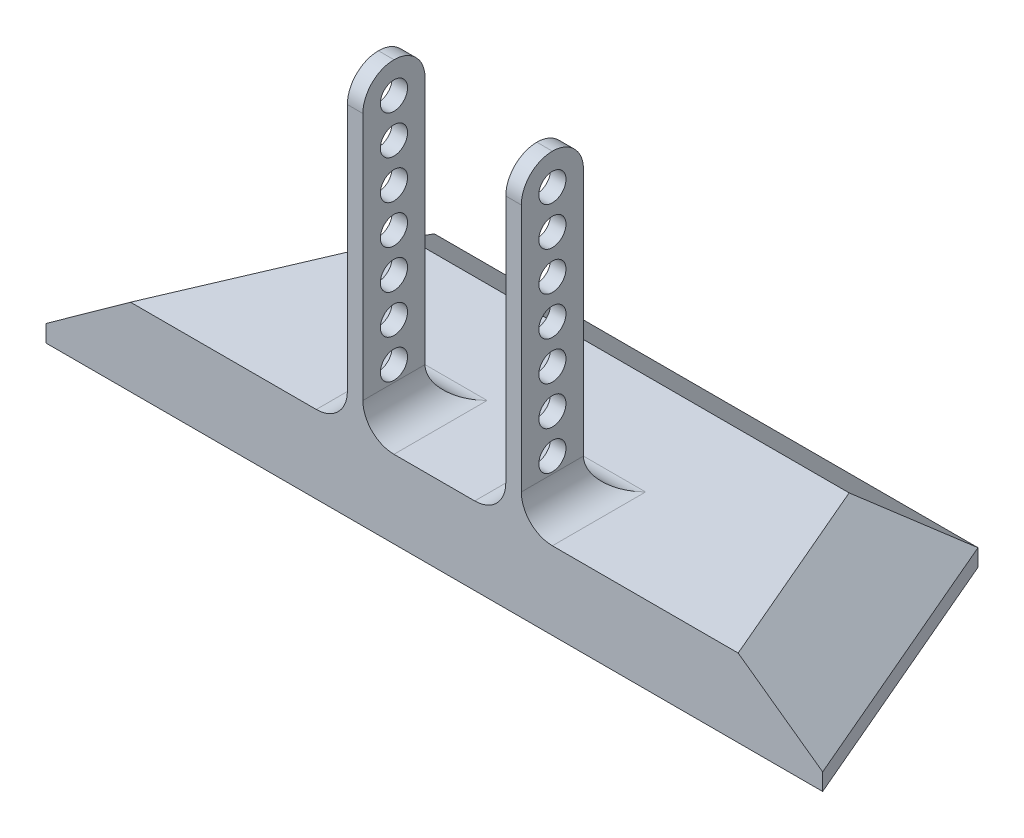
SolidWorks part; units mm, degrees
ref_plane "Front Plane" through (0, 0, 0) normal (0, 0, 1) x (1, 0, 0)
ref_plane "Top Plane" through (0, 0, 0) normal (0, 1, 0) x (1, 0, 0)
ref_plane "Right Plane" through (0, 0, 0) normal (1, 0, 0) x (0, 0, -1)
sketch "Sketch1" plane through (0, 0, 0) normal (0, 1, 0) x (1, 0, 0)
  line L1 (-50, 17.5) -> (50, 17.5)
  line L2 (-50, 17.5) -> (-50, -17.5)
  line L3 (-50, -17.5) -> (50, -17.5)
  line L4 (50, 17.5) -> (50, -17.5)
  line L5 (-50, 17.5) -> (50, -17.5) construction
  line L6 (-50, -17.5) -> (50, 17.5) construction
  point P0 (0, 0)
  dimension "D1" = 35
  dimension "D2" = 100
extrude "Boss-Extrude1" add sketch "Sketch1" along normal blind 10
sketch "Sketch2" plane through (0, 10, 0) normal (0, 1, 0) x (1, 0, 0)
  line L0 (-50, 17.5) -> (-35, 17.5)
  line L1 (50, 17.5) -> (-50, 17.5) construction
  line L2 (-35, 17.5) -> (-50, -17.5)
  line L3 (-50, -17.5) -> (-50, 17.5)
  line L4 (50, 17.5) -> (35, 17.5)
  line L5 (35, 17.5) -> (50, -17.5)
  line L6 (50, -17.5) -> (50, 17.5)
  dimension "D1" = 15
  dimension "D2" = 15
extrude "Cut-Extrude1" cut sketch "Sketch2" against normal through all
chamfer "Chamfer1" distance 10 angle 38 3 edges at (42.5, 10, 0) (-42.5, 10, 0) (0, 10, -17.5) first distance on face at (0, 10, 0)
sketch "Sketch3" plane through (0, 10, 0) normal (0, 1, 0) x (1, 0, 0)
  line L0 (-39.1203, -17.5) -> (39.1203, -17.5) construction
  line L1 (-9.2, -17.5) -> (-11.2, -17.5)
  line L2 (-9.2, -17.5) -> (-9.2, -9.5)
  line L3 (-9.2, -9.5) -> (-11.2, -9.5)
  line L4 (-11.2, -17.5) -> (-11.2, -9.5)
  dimension "D1" = 9.2
  dimension "D2" = 2
  dimension "D3" = 8
extrude "Boss-Extrude2" add sketch "Sketch3" along normal blind 40
fillet "Fillet1" radius 4 2 edges at (-10.2, 50, 9.5) (-10.2, 50, 17.5)
sketch "Sketch4" plane through (-11.2, 0, 0) normal (-1, 0, 0) x (0, 0, 1)
  line L0 (9.5, 46) -> (9.5, 10) construction
  circle A0 centre (13.5, 46) radius 1.75
  dimension "D2" = 3.5
  dimension "D1" = 4
  dimension "D3" = 4
extrude "Cut-Extrude2" cut sketch "Sketch4" against normal through all
pattern_linear "LPattern1" count 7 spacing 5 along (0, -1, 0) of "Cut-Extrude2"
mirror "Mirror1" about plane through (0, 0, 0) normal (1, 0, 0) of "LPattern1", "Cut-Extrude2", "Fillet1", "Boss-Extrude2"
fillet "Fillet2" radius 4 6 edges at (9.2, 10, 13.5) (10.2, 10, 9.5) (11.2, 10, 13.5) (-9.2, 10, 13.5) (-10.2, 10, 9.5) (-11.2, 10, 13.5)
